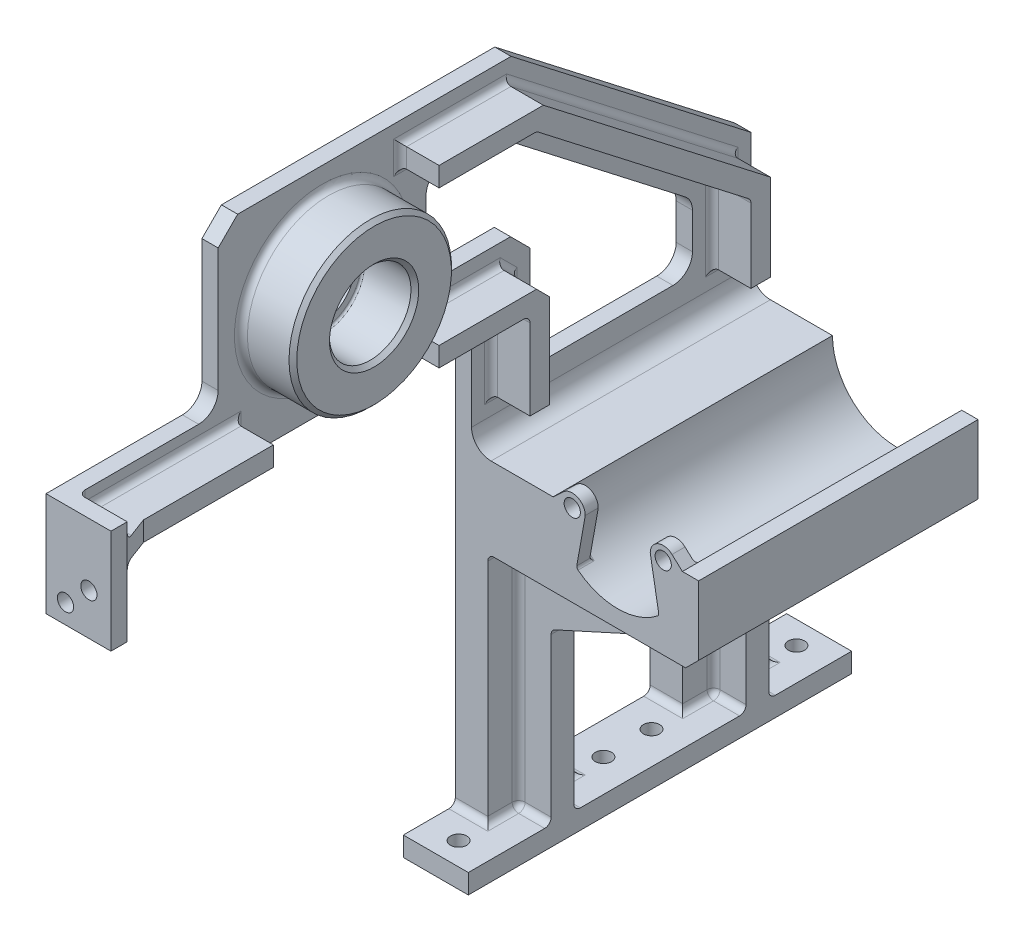
SolidWorks part; units mm, degrees
material "PLA2"
ref_plane "Front Plane" through (0, 0, 0) normal (0, 0, 1) x (1, 0, 0)
ref_plane "Top Plane" through (0, 0, 0) normal (0, 1, 0) x (1, 0, 0)
ref_plane "Right Plane" through (0, 0, 0) normal (1, 0, 0) x (0, 0, -1)
sketch "Profile-Sketch" plane through (0, 0, 0) normal (1, 0, 0) x (0, 0, -1)
  line L0 (0, 0) -> (50000, 0) construction
  line L1 (0, 0) -> (0, 50000) construction
  line L2 (0, 0) -> (0, 114.3) construction
  line L3 (0, 114.3) -> (63.5, 165.1) construction
  line L4 (63.5, 165.1) -> (190.5, 165.1) construction
  line L5 (50.8, 65.532) -> (50.8, 107.95) construction
  line L6 (35.814, 79.502) -> (65.786, 79.502) construction
  line L7 (35.814, 79.502) -> (35.814, 51.562) construction
  line L8 (35.814, 51.562) -> (65.786, 51.562) construction
  line L9 (65.786, 79.502) -> (65.786, 51.562) construction
  line L10 (35.814, 79.502) -> (65.786, 51.562) construction
  line L11 (35.814, 51.562) -> (65.786, 79.502) construction
  line L12 (35.814, 65.532) -> (65.786, 65.532) construction
  line L13 (65.786, 75.565) -> (75.692, 75.565) construction
  line L14 (75.692, 75.565) -> (75.692, 55.499) construction
  line L15 (65.786, 55.499) -> (75.692, 55.499) construction
  line L16 (75.692, 67.532) -> (80.772, 67.532) construction
  line L17 (80.772, 67.532) -> (80.772, 69.0245) construction
  line L18 (80.772, 69.0245) -> (83.312, 69.0245) construction
  line L19 (83.312, 69.0245) -> (83.312, 78.0288) construction
  line L20 (83.312, 78.0288) -> (130.302, 78.0288) construction
  line L21 (130.302, 78.0288) -> (130.302, 53.0352) construction
  line L22 (83.312, 53.0352) -> (130.302, 53.0352) construction
  line L23 (83.312, 62.0395) -> (83.312, 53.0352) construction
  line L24 (80.772, 62.0395) -> (83.312, 62.0395) construction
  line L25 (80.772, 63.532) -> (80.772, 62.0395) construction
  line L26 (75.692, 63.532) -> (80.772, 63.532) construction
  circle A0 centre (50.8, 107.95) radius 11.557 construction
  circle A1 centre (50.8, 107.95) radius 31.496 construction
  point P12 (50.8, 65.532)
  point P24 (75.692, 65.532)
  point P33 (130.302, 65.532)
  dimension "D1" = 23.114
  dimension "D8" = 62.992
  dimension "D9" = 27.94
  dimension "D2" = 107.95
  dimension "D3" = 114.3
  dimension "D4" = 50.8
  dimension "D5" = 63.5
  dimension "D6" = 50.8
  dimension "D7" = 127
  dimension "D10" = 29.972
  dimension "D11" = 20.066
  dimension "D12" = 9.906
  dimension "D13" = 42.418
  dimension "D14" = 5.08
  dimension "D15" = 2.54
  dimension "D16" = 4
  dimension "D17" = 6.985
  dimension "D18" = 24.9936
  dimension "D19" = 46.99
sketch "Sketch3" plane through (0, 0, 0) normal (1, 0, 0) x (0, 0, -1)
  line L10 (30.48, 128.27) -> (30.48, 86.36)
  line L11 (30.48, 86.36) -> (71.12, 86.36)
  line L12 (71.12, 86.36) -> (71.12, 128.27)
  line L13 (71.12, 128.27) -> (30.48, 128.27)
  line L14 (80.01, 73.66) -> (80.01, 49.53)
  line L15 (80.01, 49.53) -> (134.62, 49.53)
  line L16 (134.62, 49.53) -> (134.62, 73.66)
  line L17 (134.62, 73.66) -> (80.01, 73.66)
  circle A1 centre (50.8, 107.95) radius 6.35
  dimension "D9" = 12.7
  dimension "D1" = 20.32
  dimension "D2" = 20.32
  dimension "D3" = 20.32
  dimension "D4" = 21.59
  dimension "D5" = 54.61
  dimension "D6" = 29.21
  dimension "D7" = 34.29
  dimension "D8" = 58.42
extrude "Base-Plates" add sketch "Sketch3" along normal blind 3.175
sketch "Sketch6" plane through (3.175, 0, 0) normal (-1, 0, 0) x (0, 0, 1)
  circle A2 centre (-50.8, 107.95) radius 7.9629
  circle A3 centre (-50.8, 107.95) radius 15.875
  dimension "D1" = 15.9258
  dimension "D2" = 31.75
extrude "BearingHousing" add sketch "Sketch6" against normal blind 10.16
sketch "Sketch7" plane through (0, 0, -80.01) normal (0, 0, 1) x (1, 0, 0)
  line L2 (0, 78.0288) -> (0, 53.0352) construction
  line L3 (19.1135, 65.532) -> (44.3865, 65.532) construction
  line L8 (47.5615, 49.53) -> (47.5615, 65.532)
  line L9 (47.5615, 65.532) -> (44.3865, 65.532)
  line L10 (47.5615, 49.53) -> (3.175, 49.53)
  line L11 (3.175, 49.53) -> (3.175, 65.532)
  line L12 (3.175, 73.66) -> (3.175, 49.53) construction
  line L13 (3.175, 65.532) -> (19.1135, 65.532)
  arc A0 (19.1135, 65.532) -> (44.3865, 65.532) centre (31.75, 65.532) ccw
  point P0 (0, 107.95)
  dimension "D2" = 25.273
  dimension "D1" = 42.418
  dimension "D3" = 31.75
  dimension "D4" = 3.175
extrude "Motor-Mount" add sketch "Sketch7" against normal up to surface (54.61 mm away) up to face at (1.5875, 61.595, -134.62)
sketch "Sketch8" plane through (0, 0, -80.01) normal (0, 0, 1) x (1, 0, 0)
  line L0 (19.1135, 65.532) -> (44.3865, 65.532) construction
  line L1 (31.75, 59.182) -> (31.75, 50059.182) construction
  line L2 (19.1135, 65.532) -> (21.138, 67.3991)
  line L11 (25.4, 65.532) -> (23.6847, 55.8041)
  line L12 (23.6847, 55.8041) -> (19.1135, 55.8041)
  line L13 (19.1135, 55.8041) -> (19.1135, 65.532)
  line L14 (44.3865, 55.8041) -> (44.3865, 65.532)
  line L15 (39.8153, 55.8041) -> (44.3865, 55.8041)
  line L16 (38.1, 65.532) -> (39.8153, 55.8041)
  line L17 (44.3865, 65.532) -> (42.362, 67.3991)
  circle A0 centre (22.86, 65.532) radius 1.5875
  arc A1 (25.4, 65.532) -> (21.138, 67.3991) centre (22.86, 65.532) ccw
  arc A4 (19.1135, 65.532) -> (44.3865, 65.532) centre (31.75, 65.532) ccw construction
  arc A5 (38.1, 65.532) -> (42.362, 67.3991) centre (40.64, 65.532) cw
  circle A6 centre (40.64, 65.532) radius 1.5875
  point P2 (31.75, 65.532)
  dimension "D2" = 3.175
  dimension "D3" = 5.08
  dimension "D1" = 8.89
  dimension "D4" = 100
extrude "Motor-Mount-Holes" add sketch "Sketch8" against normal blind 2.54
sketch "Sketch9" plane through (0, 0, 0) normal (1, 0, 0) x (0, 0, -1)
  line L0 (71.12, 86.36) -> (80.01, 86.36)
  line L1 (80.01, 86.36) -> (80.01, 73.66)
  line L2 (71.12, 97.79) -> (91.44, 97.79)
  line L3 (71.12, 86.36) -> (71.12, 128.27) construction
  line L4 (91.44, 97.79) -> (91.44, 73.66)
  line L5 (134.62, 73.66) -> (80.01, 73.66) construction
  line L6 (91.44, 73.66) -> (80.01, 73.66)
  line L7 (71.12, 97.79) -> (71.12, 86.36)
  line L10 (134.62, 65.532) -> (134.62, 73.66) construction
  line L11 (134.62, 73.66) -> (123.19, 73.66)
  line L14 (71.12, 116.84) -> (71.12, 128.27)
  line L15 (71.12, 116.84) -> (83.82, 116.84)
  line L16 (83.82, 116.84) -> (123.19, 86.36)
  line L17 (123.19, 86.36) -> (123.19, 73.66)
  line L18 (71.12, 128.27) -> (87.7274, 128.27)
  line L19 (87.7274, 128.27) -> (134.62, 91.9661)
  line L20 (134.62, 91.9661) -> (134.62, 73.66)
  dimension "D1" = 11.43
  dimension "D2" = 11.43
  dimension "D3" = 11.43
  dimension "D4" = 11.43
  dimension "D5" = 11.43
  dimension "D6" = 12.7
  dimension "D7" = 12.7
extrude "Plate-Connection" add sketch "Sketch9" along normal up to surface (3.175 mm away) up to face at (3.175, 107.315, -50.8)
ref_plane "Legs-MidPlane" through (0, 0, -107.315) normal (0, 0, -1) x (-1, 0, 0)
sketch "Sketch12" plane through (0, 0, 0) normal (1, 0, 0) x (0, 0, -1)
  line L0 (80.01, 49.53) -> (96.52, 49.53)
  line L1 (134.62, 49.53) -> (80.01, 49.53) construction
  line L3 (-200000, 0) -> (250000, 0) construction
  line L4 (96.52, 0) -> (80.01, 0)
  line L5 (80.01, 0) -> (80.01, 49.53)
  line L6 (118.11, 49.53) -> (134.62, 49.53)
  line L7 (134.62, 49.53) -> (134.62, 0)
  line L8 (134.62, 0) -> (118.11, 0)
  line L12 (96.52, 49.53) -> (96.52, 0)
  line L13 (118.11, 49.53) -> (118.11, 0)
  dimension "D4" = 16.51
  dimension "D5" = 16.51
sketch "Sketch18" plane through (0, 0, 0) normal (1, 0, 0) x (0, 0, -1)
  line L0 (30.48, 96.52) -> (0, 96.52)
  line L1 (30.48, 128.27) -> (30.48, 86.36) construction
  line L2 (0, -200000) -> (0, 250000) construction
  line L3 (0, 96.52) -> (0, 86.36)
  line L4 (0, 86.36) -> (30.48, 86.36)
  line L5 (30.48, 86.36) -> (30.48, 96.52)
  line L6 (30.48, 86.36) -> (80.01, 86.36) construction
  dimension "D1" = 10.16
extrude "Bottom-Legs" add sketch "Sketch12" along normal blind 6.35
sketch "Sketch19" plane through (0, 0, 0) normal (0, -1, 0) x (1, 0, 0)
  line L0 (0, -69.85) -> (12.7, -69.85)
  line L1 (0, -30.48) -> (0, -80.01) construction
  line L2 (12.7, -69.85) -> (12.7, -144.78)
  line L3 (12.7, -144.78) -> (0, -144.78)
  line L4 (0, -144.78) -> (0, -69.85)
  line L5 (3.175, -80.01) -> (0, -80.01) construction
  line L6 (6.35, -134.62) -> (0, -134.62) construction
  dimension "D1" = 12.7
  dimension "D2" = 10.16
  dimension "D3" = 10.16
extrude "Bottom-Mount-Plate" add sketch "Sketch19" against normal blind 3.81
ref_plane "Single-Leg-MidPlane" through (0, 0, -88.265) normal (0, 0, 1) x (1, 0, 0)
sketch "Sketch20" plane through (0, 0, -88.265) normal (0, 0, 1) x (1, 0, 0)
  line L0 (40.64, 49.53) -> (12.7, 36.83)
  line L1 (47.5615, 49.53) -> (6.35, 49.53) construction
  line L2 (12.7, 36.83) -> (12.7, 6.985)
  line L3 (12.7, 6.985) -> (12.7, 3.81)
  line L4 (12.7, 3.81) -> (6.35, 3.81)
  line L5 (12.7, 3.81) -> (0, 3.81) construction
  line L6 (6.35, 3.81) -> (6.35, 49.53)
  line L7 (6.35, 49.53) -> (40.64, 49.53)
  line L8 (0, 86.36) -> (0, 3.81) construction
  dimension "D1" = 12.7
  dimension "D2" = 3.175
  dimension "D3" = 12.7
  dimension "D4" = 40.64
extrude "Leg-Stiffener" add sketch "Sketch20" along normal mid plane 4.445
mirror "Mirror1" about plane through (0, 0, -107.315) normal (0, 0, -1) of "Leg-Stiffener"
sketch "Sketch21" plane through (0, 0, 0) normal (0, -1, 0) x (1, 0, 0)
  line L0 (6.35, -134.62) -> (6.35, -128.5875) construction
  line L1 (6.35, -128.5875) -> (12.7, -128.5875) construction
  line L2 (12.7, -128.5875) -> (12.7, -144.78) construction
  line L3 (12.7, -144.78) -> (0, -144.78) construction
  line L4 (12.7, -69.85) -> (0, -69.85)
  line L5 (0, -69.85) -> (0, -144.78)
  line L6 (0, -144.78) -> (12.7, -144.78)
  line L7 (12.7, -144.78) -> (12.7, -69.85)
  line L8 (12.7, -69.85) -> (0, -69.85) construction
  line L9 (0, -69.85) -> (0, -144.78) construction
  line L10 (0, -144.78) -> (12.7, -144.78) construction
  line L11 (12.7, -144.78) -> (12.7, -69.85) construction
  line L12 (0, -144.78) -> (0, -134.62) construction
  line L13 (0, -134.62) -> (6.35, -134.62) construction
  line L14 (12.7, -69.85) -> (12.7, -86.0425) construction
  line L15 (12.7, -86.0425) -> (6.35, -86.0425) construction
  line L16 (6.35, -86.0425) -> (6.35, -80.01) construction
  line L17 (6.35, -80.01) -> (0, -80.01) construction
  line L18 (0, -80.01) -> (0, -69.85) construction
  line L19 (0, -69.85) -> (12.7, -69.85) construction
  line L20 (12.7, -124.1425) -> (6.35, -124.1425) construction
  line L21 (6.35, -124.1425) -> (6.35, -118.11) construction
  line L22 (6.35, -118.11) -> (0, -118.11) construction
  line L23 (0, -118.11) -> (0, -96.52) construction
  line L24 (0, -96.52) -> (6.35, -96.52) construction
  line L25 (6.35, -96.52) -> (6.35, -90.4875) construction
  line L26 (6.35, -90.4875) -> (12.7, -90.4875) construction
  line L27 (12.7, -90.4875) -> (12.7, -124.1425) construction
  line L28 (6.35, -134.62) -> (6.35, -128.5875) construction
  line L29 (6.35, -128.5875) -> (12.7, -128.5875) construction
  line L30 (12.7, -128.5875) -> (12.7, -144.78) construction
  line L31 (12.7, -144.78) -> (0, -144.78) construction
  line L32 (0, -144.78) -> (0, -134.62) construction
  line L33 (0, -134.62) -> (6.35, -134.62) construction
  line L34 (12.7, -69.85) -> (12.7, -86.0425) construction
  line L35 (12.7, -86.0425) -> (6.35, -86.0425) construction
  line L36 (6.35, -86.0425) -> (6.35, -80.01) construction
  line L37 (6.35, -80.01) -> (0, -80.01) construction
  line L38 (0, -80.01) -> (0, -69.85) construction
  line L39 (0, -69.85) -> (12.7, -69.85) construction
  line L40 (12.7, -124.1425) -> (6.35, -124.1425) construction
  line L41 (6.35, -124.1425) -> (6.35, -118.11) construction
  line L42 (6.35, -118.11) -> (0, -118.11) construction
  line L43 (0, -118.11) -> (0, -96.52) construction
  line L44 (0, -96.52) -> (6.35, -96.52) construction
  line L45 (6.35, -96.52) -> (6.35, -90.4875) construction
  line L46 (6.35, -90.4875) -> (12.7, -90.4875) construction
  line L47 (12.7, -90.4875) -> (12.7, -124.1425) construction
  line L48 (0, -107.315) -> (47.5615, -107.315) construction
  line L49 (47.5615, -134.62) -> (47.5615, -80.01) construction
  circle A0 centre (6.35, -74.295) radius 1.5875
  circle A1 centre (6.35, -102.616) radius 1.5875
  circle A2 centre (6.35, -140.335) radius 1.5875
  circle A3 centre (6.35, -112.014) radius 1.5875
  dimension "D2" = 3.175
  dimension "D7" = 3.175
  dimension "D3" = 6.35
  dimension "D4" = 33.02
  dimension "D5" = 4.699
  dimension "D6" = 6.35
  dimension "D8" = 74.295
  dimension "D9" = 102.616
  dimension "D10" = 112.014
  dimension "D11" = 140.335
extrude "Bottom-Mount-Holes" cut sketch "Sketch21" against normal up to surface (3.81 mm away) up to face at (6.35, 3.81, -107.315)
extrude "Side-Arm" add sketch "Sketch18" along normal up to surface (3.175 mm away) up to face at (3.175, 94.7057, -93.6171)
sketch "Sketch22" plane through (0, 0, 0) normal (0, 0, 1) x (1, 0, 0)
  line L0 (0, 96.52) -> (12.7, 96.52)
  line L1 (12.7, 96.52) -> (12.7, 76.2)
  line L2 (12.7, 76.2) -> (0, 76.2)
  line L3 (0, 86.36) -> (0, 3.81) construction
  line L4 (0, 76.2) -> (0, 96.52)
  line L5 (3.175, 86.36) -> (0, 86.36) construction
  dimension "D1" = 12.7
  dimension "D2" = 10.16
extrude "Side-Arm-Plate" add sketch "Sketch22" against normal blind 3.175
ref_plane "Arm-MidPlane" through (0, 91.44, 0) normal (0, 1, 0) x (1, 0, 0)
sketch "Sketch23" plane through (0, 91.44, 0) normal (0, 1, 0) x (1, 0, 0)
  line L0 (3.175, 33.655) -> (10.795, 33.655)
  line L1 (3.175, 87.7274) -> (3.175, 30.48) construction
  line L2 (10.795, 33.655) -> (10.795, 8.255)
  line L3 (10.795, 8.255) -> (12.7, 3.175)
  line L4 (3.175, 33.655) -> (3.175, 3.175)
  line L5 (3.175, 3.175) -> (12.7, 3.175)
  line L6 (0, 30.48) -> (0, 0) construction
  line L7 (3.175, 34.925) -> (13.335, 34.925) construction
  dimension "D1" = 10.795
  dimension "D2" = 5.08
  dimension "D3" = 1.27
extrude "Arm-Stiffener" add sketch "Sketch23" along normal mid plane 3.81
sketch "Sketch24" plane through (0, 0, -3.175) normal (0, 0, -1) x (-1, 0, 0)
  line L1 (0, 3.81) -> (0, 91.9661) construction
  line L2 (0, 91.9661) -> (0, 128.27) construction
  line L3 (0, 76.2) -> (-12.7, 76.2) construction
  circle A0 centre (-8.382, 84.328) radius 1.5875
  circle A1 centre (-3.81, 80.01) radius 1.5875
  dimension "D1" = 3.175
  dimension "D2" = 3.175
  dimension "D3" = 8.382
  dimension "D4" = 3.81
  dimension "D5" = 8.128
  dimension "D6" = 3.81
  dimension "D7" = 84.328
  dimension "D8" = 80.01
extrude "Side-Mount-Holes" cut sketch "Sketch24" against normal up to surface (3.175 mm away) up to face at (6.35, 86.36, 0)
fillet "Fillet1" radius 1.27 28 edges at (6.35, 49.53, -93.5037) (6.35, 49.53, -131.6037) (6.35, 3.81, -121.1263) (3.175, 3.81, -80.01) (6.35, 3.81, -83.0262) (3.175, 3.81, -96.52) (3.175, 3.81, -134.62) (3.175, 3.81, -118.11) (6.35, 3.81, -93.5037) (6.35, 49.53, -83.0262) (23.495, 49.53, -90.4875) (40.64, 49.53, -88.265) (6.35, 26.67, -90.4875) (9.525, 3.81, -90.4875) (12.7, 36.83, -88.265) (23.495, 49.53, -86.0425) (6.35, 26.67, -86.0425) (9.525, 3.81, -86.0425) (6.35, 3.81, -131.6038) (6.35, 49.53, -121.1263) (23.495, 49.53, -128.5875) (40.64, 49.53, -126.365) (12.7, 36.83, -126.365) (9.525, 3.81, -128.5875) (6.35, 26.67, -128.5875) (23.495, 49.53, -124.1425) (6.35, 26.67, -124.1425) (9.525, 3.81, -124.1425)
fillet "Fillet2" radius 3.81 11 edges at (1.5875, 96.52, -30.48) (1.5875, 86.36, -80.01) (3.175, 65.532, -107.315) (1.5875, 86.36, -123.19) (1.5875, 116.84, -83.82) (1.5875, 116.84, -71.12) (1.5875, 97.79, -71.12) (1.5875, 73.66, -91.44) (1.5875, 73.66, -123.19) (3.81, 49.53, -96.52) (3.81, 49.53, -118.11)
fillet "Fillet3" radius 1.27 8 edges at (1.5875, 86.36, -3.175) (3.175, 87.9475, -3.175) (3.175, 89.535, -18.415) (7.9375, 89.535, -3.175) (3.175, 93.345, -18.415) (3.175, 94.9325, -3.175) (7.9375, 93.345, -3.175) (3.175, 91.44, -33.655)
chamfer "Chamfer1" distance 3.81 angle 45 2 edges at (1.5875, 128.27, -30.48) (1.5875, 97.79, -91.44)
fillet "Fillet4" radius 0.635 4 edges at (23.6847, 55.8041, -81.28) (39.8153, 55.8041, -81.28) (43.1867, 60.1578, -82.55) (20.3133, 60.1578, -82.55)
chamfer "Chamfer2" distance 0.762 angle 45 2 edges at (13.335, 107.95, -42.8371) (13.335, 107.95, -34.925)
sketch "Sketch25" plane through (3.175, 0, 0) normal (1, 0, 0) x (0, 0, -1)
  line L0 (68.2212, 122.555) -> (85.7737, 122.555) construction
  line L1 (85.7737, 122.555) -> (128.905, 89.163) construction
  line L2 (128.905, 89.163) -> (128.905, 72.2985) construction
  line L3 (84.8499, 116.0427) -> (121.7124, 87.504) construction
  line L4 (94.6916, 108.4233) -> (101.6887, 117.4613) construction
  line L5 (134.62, 91.9661) -> (87.7274, 128.27) construction
  line L6 (123.19, 81.9861) -> (134.62, 81.9861) construction
  line L7 (123.19, 84.4913) -> (123.19, 77.47) construction
  line L8 (134.62, 69.342) -> (134.62, 91.9661) construction
  line L9 (77.1343, 97.79) -> (77.1343, 86.36) construction
  line L10 (87.63, 97.79) -> (74.93, 97.79) construction
  line L11 (4.445, 86.36) -> (76.2, 86.36) construction
  line L12 (80.01, 82.6135) -> (91.44, 82.6135) construction
  line L13 (80.01, 82.55) -> (80.01, 69.342) construction
  line L14 (91.44, 77.47) -> (91.44, 93.98) construction
  line L15 (80.2651, 128.27) -> (80.2651, 116.84) construction
  line L16 (87.7274, 128.27) -> (34.29, 128.27) construction
  line L17 (74.93, 116.84) -> (82.5175, 116.84) construction
  line L18 (66.04, 124.46) -> (66.04, 120.65)
  line L19 (66.04, 120.65) -> (85.1225, 120.65)
  line L20 (85.1225, 120.65) -> (127, 88.2287)
  line L21 (127, 88.2287) -> (127, 73.152)
  line L22 (127, 73.152) -> (130.81, 73.152)
  line L23 (130.81, 73.152) -> (130.81, 90.0974)
  line L24 (130.81, 90.0974) -> (86.425, 124.46)
  line L25 (86.425, 124.46) -> (66.04, 124.46)
  line L26 (108.6175, 107.2787) -> (106.2851, 104.266) construction
  line L27 (127, 78.9541) -> (130.81, 78.9541) construction
  line L28 (134.62, 65.532) -> (83.185, 65.532) construction
  line L29 (66.04, 92.075) -> (85.725, 92.075) construction
  line L30 (85.725, 92.075) -> (85.725, 73.152) construction
  line L31 (66.04, 93.98) -> (87.63, 93.98)
  line L32 (87.63, 93.98) -> (87.63, 73.152)
  line L33 (87.63, 73.152) -> (83.82, 73.152)
  line L34 (83.82, 73.152) -> (83.82, 90.17)
  line L35 (83.82, 90.17) -> (66.04, 90.17)
  line L36 (66.04, 90.17) -> (66.04, 93.98)
  circle A0 centre (50.8, 107.95) radius 6.35 construction
  point P10 (98.1902, 112.9423)
  point P29 (77.1343, 92.075)
  point P30 (85.725, 82.6135)
  point P31 (128.905, 81.9861)
  point P32 (80.2651, 122.555)
  point P47 (107.4513, 105.7724)
  point P48 (66.04, 122.555)
  point P49 (128.905, 78.9541)
  dimension "D1" = 3.81
  dimension "D2" = 3.81
  dimension "D3" = 3.81
  dimension "D4" = 15.24
  dimension "D5" = 7.62
  dimension "D6" = 3.81
  dimension "D7" = 3.81
  dimension "D8" = 7.62
  dimension "D9" = 15.24
extrude "Mid-Stiffeners" add sketch "Sketch25" along normal blind 7.62
chamfer "Chamfer3" distance 2.54 angle 45 1 edges at (6.985, 93.98, -87.63)
fillet "Fillet6" radius 1.27 18 edges at (3.175, 124.46, -76.2325) (3.175, 122.555, -66.04) (6.985, 120.65, -85.1225) (3.175, 120.65, -75.5812) (3.175, 107.2787, -108.6175) (3.175, 81.6247, -130.81) (3.175, 73.152, -128.905) (3.175, 104.4393, -106.0612) (6.985, 88.2287, -127) (3.175, 80.6903, -127) (3.175, 73.152, -85.725) (3.175, 92.075, -66.04) (3.175, 93.98, -75.565) (3.175, 92.71, -86.36) (3.175, 82.296, -87.63) (3.175, 81.661, -83.82) (6.985, 90.17, -83.82) (3.175, 90.17, -74.93)
chamfer "Chamfer4" distance 2.54 angle 45 1 edges at (47.5615, 49.53, -107.315)
fillet "Fillet7" radius 1.27 1 edges at (3.175, 107.95, -34.925)
fillet "Fillet8" radius 0.381 1 edges at (3.175, 107.95, -58.7629)
ref_plane "Plane1" through (8.255, 0, 0) normal (1, 0, 0) x (0, 0, -1)
sketch "Sketch26" plane through (8.255, 0, 0) normal (1, 0, 0) x (0, 0, -1)
  circle A1 centre (50.8, 107.95) radius 7.5819
  circle A2 centre (50.8, 107.95) radius 7.5819 construction
  point P1 (50.8, 107.95)
  dimension "D1" = 0
equation "\"D2@Sketch9\"=\"D1@Sketch9\""
equation "\"D3@Sketch9\"=\"D1@Sketch9\""
equation "\"D4@Sketch9\"=\"D1@Sketch9\""
equation "\"D5@Sketch9\"=\"D1@Sketch9\""
equation "\"D5@Sketch12\"=\"D4@Sketch12\""
equation "\"D7@Sketch21\"=\"D2@Sketch21\""
equation "\"D2@Sketch25\"=\"D1@Sketch25\""
equation "\"D3@Sketch25\"=\"D1@Sketch25\""
equation "\"D7@Sketch25\"=\"D1@Sketch25\""
equation "\"D6@Sketch25\"=\"D1@Sketch25\""
